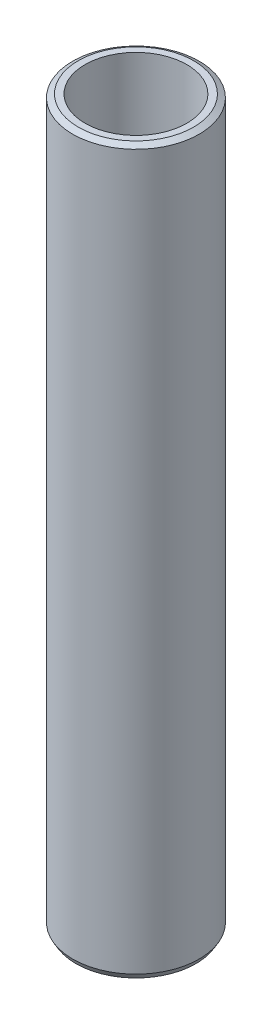
SolidWorks part; units mm, degrees
ref_plane "Front Plane" through (0, 0, 0) normal (0, 0, 1) x (1, 0, 0)
ref_plane "Top Plane" through (0, 0, 0) normal (0, 1, 0) x (1, 0, 0)
ref_plane "Right Plane" through (0, 0, 0) normal (1, 0, 0) x (0, 0, -1)
sketch "Sketch1" plane through (0, 0, 0) normal (0, 1, 0) x (1, 0, 0)
  circle A0 centre (0, 0) radius 52.5
  dimension "SHAFT_OD" = 105
extrude "Boss-Extrude1" add sketch "Sketch1" along normal blind 600
sketch "Sketch2" plane through (0, 0, 0) normal (0, 1, 0) x (1, 0, 0)
  circle A0 centre (0, 0) radius 42.2148
  dimension "BORE_D" = 84.4295
extrude "Cut-Extrude1" cut sketch "Sketch2" along normal through all
chamfer "Chamfer1" distance 2.7017 angle 60 2 edges at (0, 600, 52.5) (0, 0, 52.5) first distance on face at (0, 600, 52.5) first distance on face at (0, 0, 42.2148)
